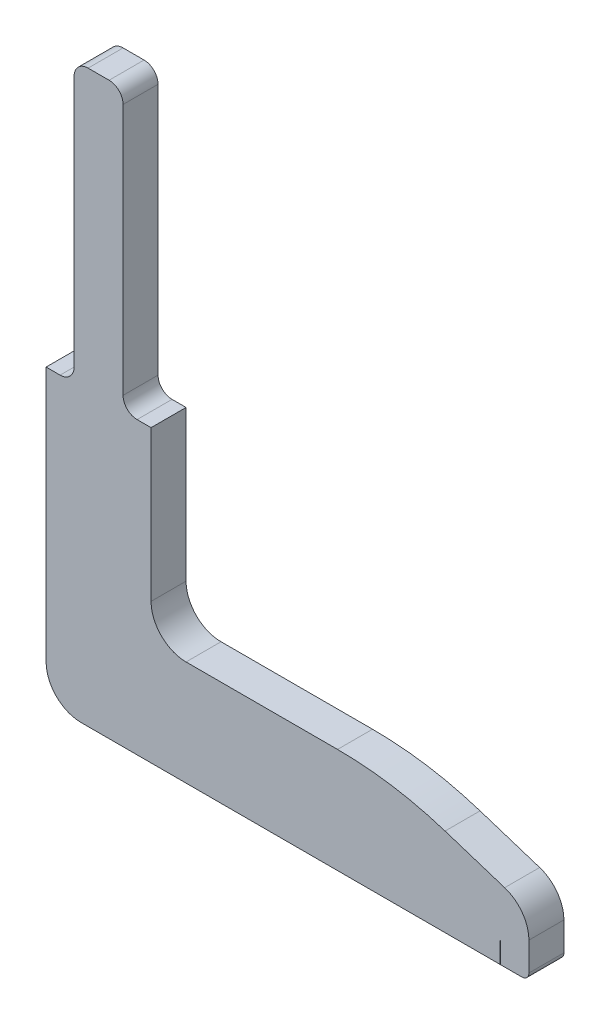
SolidWorks part; units mm, degrees
ref_plane "Front Plane" through (0, 0, 0) normal (0, 0, 1) x (1, 0, 0)
ref_plane "Top Plane" through (0, 0, 0) normal (0, 1, 0) x (1, 0, 0)
ref_plane "Right Plane" through (0, 0, 0) normal (1, 0, 0) x (0, 0, -1)
sketch "Sketch1" plane through (0, 0, 0) normal (0, 0, 1) x (1, 0, 0)
  line L0 (0, -1) -> (0, -36.5)
  line L1 (5, -41.5) -> (68, -41.5)
  line L2 (69, -40.5) -> (69, -36.43)
  line L3 (41.65, -26.5) -> (20, -26.5)
  line L4 (15, -21.5) -> (15, -1)
  line L5 (14, 0) -> (11, 0)
  line L6 (15, -1) -> (15, 0)
  line L7 (15, 0) -> (14, 0)
  line L8 (0, -1) -> (0, 0)
  line L9 (0, 0) -> (1, 0)
  line L10 (65.5369, -31.6721) -> (57.0187, -28.9206)
  line L11 (4, 0) -> (4, 40)
  line L12 (11, 0) -> (11, 40)
  line L13 (11, 40) -> (4, 40)
  line L14 (4, 0) -> (1, 0)
  arc A2 (69, -40.5) -> (68, -41.5) centre (68, -40.5) cw
  arc A4 (5, -41.5) -> (0, -36.5) centre (5, -36.5) cw
  arc A5 (15, -21.5) -> (20, -26.5) centre (20, -21.5) ccw
  arc A6 (65.5369, -31.6721) -> (69, -36.43) centre (64, -36.43) cw
  arc A7 (41.65, -26.5) -> (57.0187, -28.9206) centre (41.65, -76.5) cw
  point P9 (0, 0)
  point P12 (15, 0)
  point P15 (69, -41.5)
  point P18 (69, -26.5)
  point P21 (0, -41.5)
  point P24 (15, -26.5)
  dimension "D6" = 5
  dimension "D5" = 5
  dimension "D7" = 50
  dimension "D1" = 26.5
  dimension "D2" = 15
  dimension "D3" = 69
  dimension "D4" = 15
  dimension "D8" = 4
  dimension "D9" = 4
  dimension "D10" = 40
extrude "Boss-Extrude1" add sketch "Sketch1" along normal blind 5
sketch "Sketch2" plane through (0, -41.5, 0) normal (0, -1, 0) x (1, 0, 0)
  line L0 (0, 2.5) -> (64.9, 2.5) construction
  line L1 (0, 5) -> (0, 0) construction
  line L2 (5, 5) -> (68, 5) construction
  line L3 (64.85, 0) -> (64.95, 0)
  line L4 (64.85, 0) -> (64.85, 5)
  line L5 (64.85, 5) -> (64.95, 5)
  line L6 (64.95, 0) -> (64.95, 5)
  line L7 (64.85, 0) -> (64.95, 5) construction
  line L8 (64.85, 5) -> (64.95, 0) construction
  dimension "D1" = 64.9
  dimension "D2" = 0.1
extrude "Cut-Extrude2" cut sketch "Sketch2" against normal blind 3
fillet "Fillet1" radius 2 4 edges at (4, 40, 2.5) (11, 40, 2.5) (4, 0, 2.5) (11, 0, 2.5)
equation "\"A.L\"= 0.07m"
equation "\"A.h\"= 0.007m"
equation "\"A.d\"= 0.005m"
equation "\"A.delta\"= 45.0001"
equation "\"A.w\"= 0m"
equation "\"A.v\"= 0.013m"
equation "\"A.s\"= 0.014m"
equation "\"A.t\"= 0.007m"
equation "\"B.L\"= 0.065m"
equation "\"B.h\"= 0.008m"
equation "\"B.s\"= 0.016m"
equation "\"B.t\"= 0.008m"
equation "\"C.h\"= 0.0065m"
equation "\"C.d\"= 0.005m"
equation "\"C.L\"= 0.05m"
equation "\"C.wmax\"= 0.003m"
equation "\"D.L\"= 0.06m"
equation "\"D.h\"= 0.008m"
equation "\"D.s\"= 0.012m"
equation "\"D.t\"= 0.008m"
equation "\"a_h\"= 0.0001m"
equation "\"a_d\"= 0.005m"
equation "\"a_L\"= 0.008m"
equation "\"b_h\"= 0.0004m"
equation "\"b_d\"= 0.005m"
equation "\"b_L\"= 0.007m"
equation "\"c_h\"= 0.0001m"
equation "\"c_d\"= 0.005m"
equation "\"c_L\"= 0.01m"
equation "\"d_h\"= 0.0001m"
equation "\"d_d\"= 0.005m"
equation "\"d_L\"= 0.01m"
equation "\"S.h\"= 0.015m"
equation "\"S.L\"= 0.09275m"
equation "\"D1@Sketch1\"=\"S.L\"-\"C.wmax\"-\"C.h\"/2-60mm"
equation "\"D2@Sketch1\"=\"S.h\""
equation "\"D3@Sketch1\"=\"C.L\"+\"S.h\"+0.004"
equation "\"D4@Sketch1\"=\"S.h\""
equation "\"D1@Boss-Extrude1\"=0.005m"
equation "\"D1@Sketch2\"=\"C.L\"+\"S.h\"-\"d_h\""
equation "\"D2@Sketch2\"=\"d_h\""
